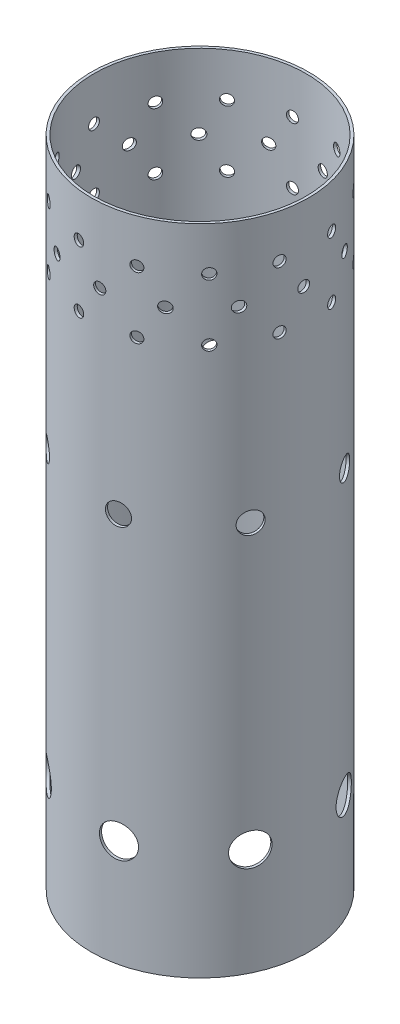
SolidWorks part; units mm, degrees
material "Plain Carbon Steel"
ref_plane "Front Plane" through (0, 0, 0) normal (0, 0, 1) x (1, 0, 0)
ref_plane "Top Plane" through (0, 0, 0) normal (0, 1, 0) x (1, 0, 0)
ref_plane "Right Plane" through (0, 0, 0) normal (1, 0, 0) x (0, 0, -1)
sketch "Sketch2" plane through (0, 0, 0) normal (0, 1, 0) x (1, 0, 0)
  circle A0 centre (0, 0) radius 63.5
  circle A1 centre (0, 0) radius 61.9125
  dimension "D1" = 1.5875
extrude "Boss-Extrude1" add sketch "Sketch2" along normal blind 381
sketch "Sketch3" plane through (0, 0, 0) normal (1, 0, 0) x (0, 0, -1)
  line L0 (0, 381) -> (0, 355.6) construction
  line L1 (61.9125, 381) -> (-61.9125, 381) construction
  line L2 (0, 355.6) -> (17.9605, 337.6395) construction
  line L3 (17.9605, 337.6395) -> (0, 319.679) construction
  circle A0 centre (0, 355.6) radius 3.175
  circle A1 centre (17.9605, 337.6395) radius 3.175
  circle A2 centre (0, 319.679) radius 3.175
extrude "Cut-Extrude1" cut sketch "Sketch3" against normal blind 381
pattern_circular "CirPattern1" count 13 over 360 about axis through (0, 381, 0) along (0, -1, 0) of "Cut-Extrude1"
sketch "Sketch4" plane through (0, 0, 0) normal (1, 0, 0) x (0, 0, -1)
  line L0 (0, 381) -> (0, 227.473) construction
  line L1 (63.5, 381) -> (-63.5, 381) construction
  line L2 (0, 227.473) -> (0, 62.373) construction
  circle A0 centre (0, 227.473) radius 6.35
  circle A1 centre (0, 62.373) radius 9.525
extrude "Cut-Extrude2" cut sketch "Sketch4" against normal blind 381
pattern_circular "CirPattern2" count 7 over 360 about axis through (0, 381, 0) along (0, -1, 0) of "Cut-Extrude2"
